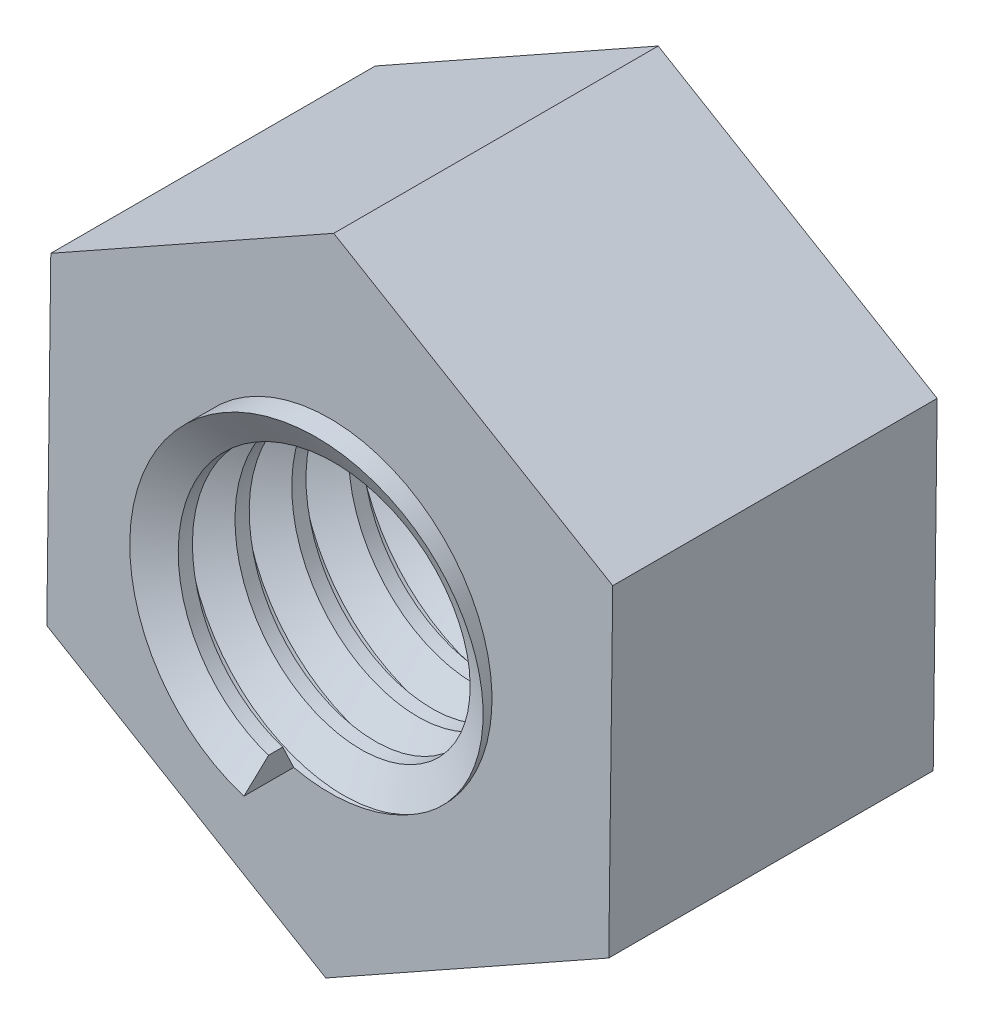
SolidWorks part; units mm, degrees
ref_plane "Front Plane" through (0, 0, 0) normal (0, 0, 1) x (1, 0, 0)
ref_plane "Top Plane" through (0, 0, 0) normal (0, 1, 0) x (1, 0, 0)
ref_plane "Right Plane" through (0, 0, 0) normal (1, 0, 0) x (0, 0, -1)
sketch "Sketch1" plane through (0, 0, 0) normal (0, 0, 1) x (1, 0, 0)
  line L1 (8.5989, -5.1062) -> (8.7216, 4.8938)
  line L2 (8.7216, 4.8938) -> (0.1227, 10)
  line L3 (0.1227, 10) -> (-8.5989, 5.1062)
  line L4 (-8.5989, 5.1062) -> (-8.7216, -4.8938)
  line L5 (-8.7216, -4.8938) -> (-0.1227, -10)
  line L6 (-0.1227, -10) -> (8.5989, -5.1062)
  circle A0 centre (0, 0) radius 8.6609 construction
  dimension "D1" = 20
extrude "Boss-Extrude1" add sketch "Sketch1" along normal blind 10
sketch "Sketch2" plane through (0, 0, 0) normal (0, 0, -1) x (-1, 0, 0)
  circle A0 centre (0, 0) radius 5
  dimension "D1" = 10
extrude "Cut-Extrude1" cut sketch "Sketch2" against normal through all
thread "Thread1" pitch 1.75 method extrude profile "Thread Profile3" start angle 0, offset 0, length 0, pitch 1.75, diameter 10
ref_plane "Plane3" through (5, 0, 0) normal (0, -1, 0) x (1, 0, 0)
sketch "Thread Profile3" plane through (5, 0, 0) normal (0, -1, 0) x (1, 0, 0)
  line L0 (0, 0) -> (0, 1.75) construction
  line L11 (0, 0) -> (0, 1.5312)
  line L12 (0, 1.5312) -> (-0.9472, 0.9844)
  line L13 (-0.9472, 0.9844) -> (-0.9472, 0.5469)
  line L15 (-0.9472, 0.5469) -> (0, 0)
  line L17 (-0.9472, 0.7656) -> (0, 0.7656) construction
  point P2 (0, 0)
  dimension "Pitch" = 1.75
  dimension "Profile_Angle" = 60
  dimension "Profile_Land" = 0.4375
  dimension "Profile_Height" = 0.9472
